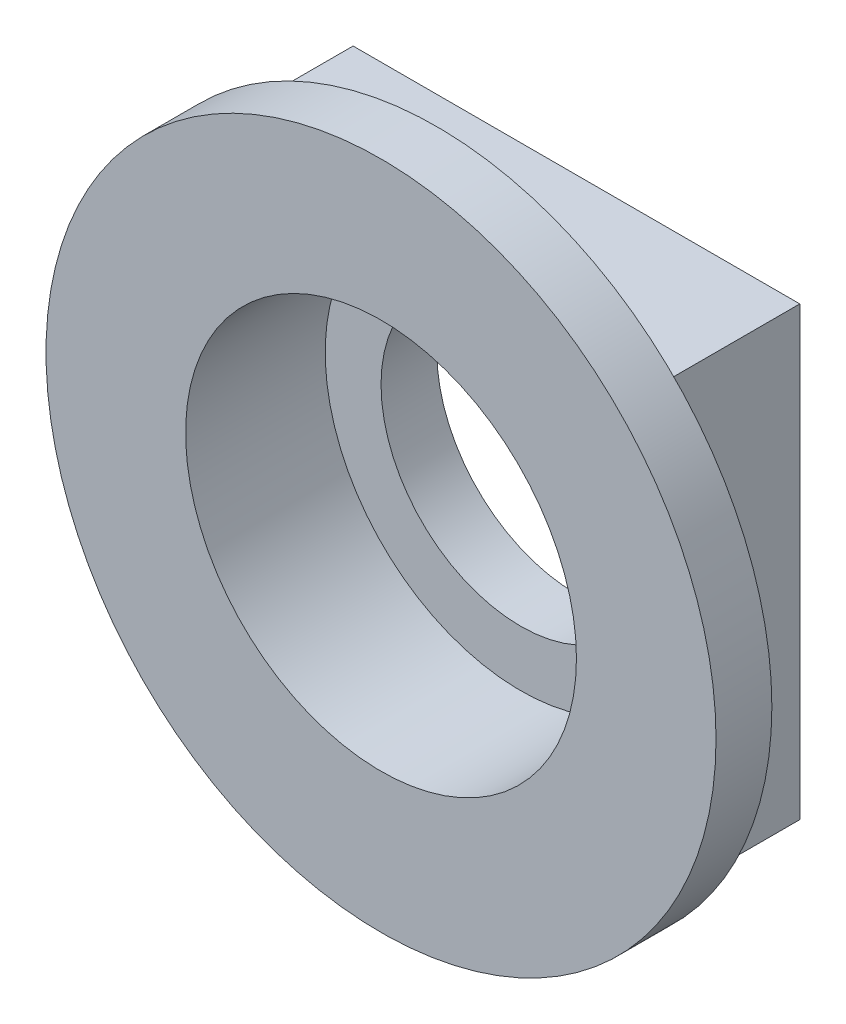
SolidWorks part; units mm, degrees
material "2014-T6"
ref_plane "Ebene vorne" through (0, 0, 0) normal (0, 0, 1) x (1, 0, 0)
ref_plane "Ebene oben" through (0, 0, 0) normal (0, 1, 0) x (1, 0, 0)
ref_plane "Ebene rechts" through (0, 0, 0) normal (1, 0, 0) x (0, 0, -1)
sketch "Skizze1" plane through (0, 0, 0) normal (0, 0, 1) x (1, 0, 0)
  line L0 (-4, 0) -> (4, 0) construction
  line L1 (-4, 4) -> (4, 4)
  line L2 (-4, 4) -> (-4, -4)
  line L3 (-4, -4) -> (4, -4)
  line L4 (4, 4) -> (4, -4)
  circle A0 centre (0, 0) radius 3.5
  circle A1 centre (0, 0) radius 6
  circle A2 centre (0, 0) radius 2.5
  dimension "D1" = 7
  dimension "D2" = 12
  dimension "D3" = 5
  dimension "D4" = 8
extrude "Aufsatz-Linear austragen1" add sketch "Skizze1" against normal blind 3.5 contours A1
extrude "Schnitt-Linear austragen1" cut sketch "Skizze1<3>" against normal blind 2.5 contours A0
sketch "Skizze1<3>" plane through (0, 0, 0) normal (0, 0, 1) x (1, 0, 0) same geometry as "Skizze1"
extrude "Schnitt-Linear austragen3" cut sketch "Skizze1<4>" against normal through all contours A2
sketch "Skizze1<4>" plane through (0, 0, 0) normal (0, 0, 1) x (1, 0, 0) same geometry as "Skizze1"
extrude "Schnitt-Linear austragen4" cut sketch "Skizze1<5>" against normal through all from offset 1 flip side to cut contours L2 L3 L4 L1
sketch "Skizze1<5>" plane through (0, 0, 0) normal (0, 0, 1) x (1, 0, 0) same geometry as "Skizze1"
